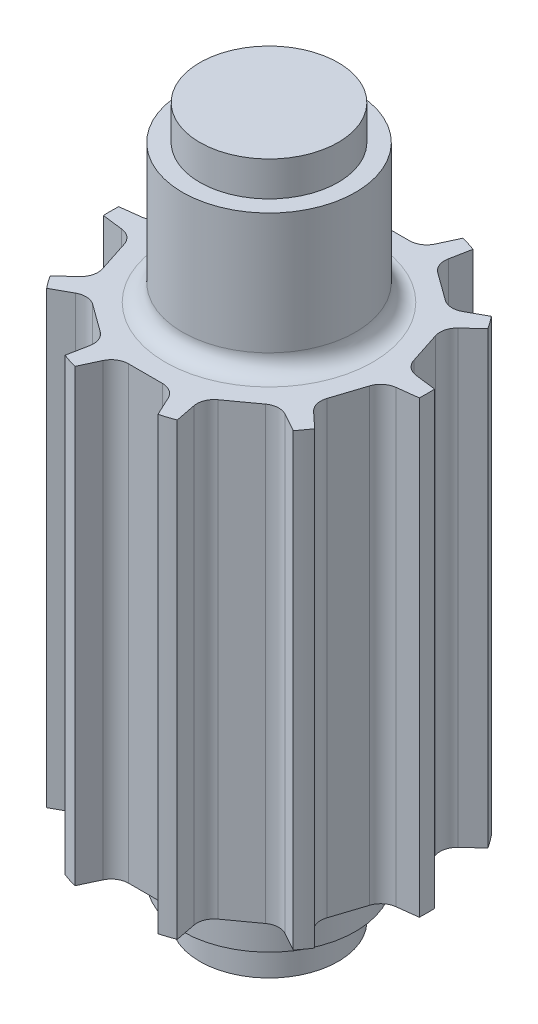
SolidWorks part; units mm, degrees
material "6061-T6 (SS)"
ref_plane "Ebene vorne" through (0, 0, 0) normal (0, 0, 1) x (1, 0, 0)
ref_plane "Ebene oben" through (0, 0, 0) normal (0, 1, 0) x (1, 0, 0)
ref_plane "Ebene rechts" through (0, 0, 0) normal (1, 0, 0) x (0, 0, -1)
ref_axis "Achse1" through (0, -12.75, 0) along (0, 1, 0)
sketch "Skizze1" plane through (0, 0, 0) normal (0, 1, 0) x (1, 0, 0)
  circle A0 centre (0, 0) radius 4.57
  circle A1 centre (0, 0) radius 2
  dimension "D1" = 9.14
  dimension "D2" = 4
extrude "Aufsatz-Linear austragen1" add sketch "Skizze1" along normal blind 13
sketch "Skizze12" plane through (0, 13, 0) normal (0, 1, 0) x (1, 0, 0)
  line L0 (0, 9.2022) -> (0, -8.7185) construction
  line L1 (-8.4713, 0) -> (7.9602, 0) construction
  line L2 (-1.2, 4.4096) -> (-0.8085, 3.57)
  line L3 (1.2, 4.4096) -> (0.8085, 3.57)
  line L4 (-2.8195, 3.57) -> (2.5735, 3.57) construction
  line L5 (-2.9704, 4.57) -> (2.868, 4.57) construction
  line L6 (-0.8085, 3.57) -> (0.8085, 3.57)
  circle A1 centre (0, 0) radius 4.57 construction
  circle A2 centre (0, 0) radius 4.57 construction
  arc A4 (-1.2, 4.4096) -> (1.2, 4.4096) centre (0, 0) cw
  dimension "D1" = 1
  dimension "D5" = 1.6169
  dimension "D6" = 9.14
  dimension "D2" = 2.4
  dimension "D3" = 50
  dimension "D4" = 3.57
extrude "Schnitt-Linear austragen1" cut sketch "Skizze12" against normal through all
fillet "Verrundung1" radius 0.5 2 edges at (0.8085, 6.5, -3.57) (-0.8085, 6.5, -3.57)
pattern_circular "Kreismuster1" count 10 over 360 about axis through (0, -12.75, 0) along (0, 1, 0) of "Schnitt-Linear austragen1", "Verrundung1"
chamfer "Fase2" distance 0.2 angle 45 2 edges at (0, 13, 2) (0, 0, 2)
ref_plane "Plane1" through (0, 6.5, 0) normal (0, -1, 0) x (-1, 0, 0)
sketch "Sketch1" plane through (0, 6.5, 0) normal (0, -1, 0) x (-1, 0, 0)
  line L0 (0, 0) -> (0, -5.2371) construction
  line L1 (0, -5.2371) -> (0, 5.3993) construction
  line L2 (-1.4, -5.2371) -> (-1.4, 5.3993) construction
  line L3 (-1.4, 1.4283) -> (-1.4, -1.4283)
  circle A0 centre (0, 0) radius 2 construction
  circle A1 centre (0, 0) radius 2 construction
  arc A2 (-1.4, 1.4283) -> (-1.4, -1.4283) centre (0, 0) ccw
  dimension "D1" = 1.4
ref_plane "Plane2" through (0, 12.8, 0) normal (0, -1, 0) x (-1, 0, 0)
ref_plane "Plane3" through (0, 0.2, 0) normal (0, 1, 0) x (1, 0, 0)
extrude "Boss-Extrude1" add sketch "Sketch1" against normal up to surface (6.3 mm away) and the other way up to surface (6.3 mm away) up to plane "Plane2" other way up to plane "Plane3"
sketch "Sketch2" plane through (0, 13, 0) normal (0, 1, 0) x (1, 0, 0)
  circle A0 centre (0, 0) radius 2.2
  dimension "D1" = 4.4
extrude "Boss-Extrude4" add sketch "Sketch2" against normal up to surface (13 mm away) separate body up to face at (0, 0, 2.2)
sketch "Sketch3" plane through (0, 13, 0) normal (0, 1, 0) x (1, 0, 0)
  circle A0 centre (0, 0) radius 2
  dimension "D1" = 4
extrude "Boss-Extrude6" add sketch "Sketch3" along normal blind 5 and the other way blind 15.5
fillet "Fillet2" radius 0.5 2 edges at (0, 0, 2) (0, 13, 2)
sketch "Sketch4" plane through (0, 0, 0) normal (0, -1, 0) x (1, 0, 0)
  circle A0 centre (0, 0) radius 2 construction
  circle A1 centre (0, 0) radius 2 construction
  circle A2 centre (0, 0) radius 1.5
  circle A3 centre (0, 0) radius 2.5
  dimension "D1" = 0.5
  dimension "D2" = 0.5
extrude "Boss-Extrude7" add sketch "Sketch4" along normal offset from surface (1.5 mm away) 1 up to face at (0, -2.5, 2)
fillet "Fillet3" radius 0.25 1 edges at (0, 0, -2.5)
sketch "Sketch5" plane through (0, 13, 0) normal (0, 1, 0) x (1, 0, 0)
  circle A0 centre (0, 0) radius 2 construction
  circle A1 centre (0, 0) radius 2 construction
  circle A2 centre (0, 0) radius 2.5
  circle A3 centre (0, 0) radius 1.5
  dimension "D1" = 0.5
  dimension "D2" = 0.5
extrude "Boss-Extrude8" add sketch "Sketch5" along normal offset from surface (4 mm away) 1 up to face at (0, 18, 2)
fillet "Fillet4" radius 0.5 1 edges at (0, 13, 2.5)
